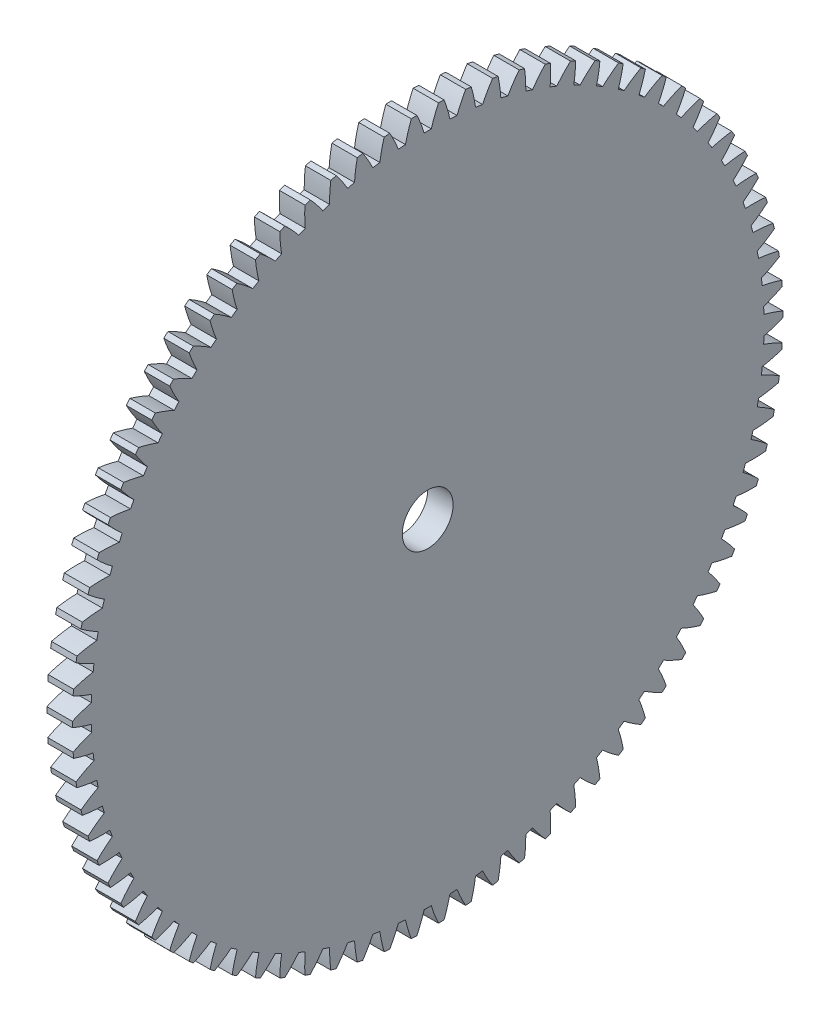
SolidWorks part; units mm, degrees
ref_plane "Plane1" through (0, 0, 0) normal (0, 0, 1) x (1, 0, 0)
ref_plane "Plane2" through (0, 0, 0) normal (0, 1, 0) x (1, 0, 0)
ref_plane "Plane3" through (0, 0, 0) normal (1, 0, 0) x (0, 0, -1)
sketch "HoldingSke" plane through (0, 0, 0) normal (0, 1, 0) x (1, 0, 0)
  line L0 (0, 0) -> (0.1392, -0.9903)
  line L1 (-15, 0) -> (100, 0) construction
  line L2 (0, 0) -> (-2.1039, 2.3779)
  line L3 (0, 0) -> (-11.863, 4.5341)
  line L4 (0, 0) -> (1.2019, 8.552)
  line L5 (0, 0) -> (-46.8476, -17.4728)
  line L6 (0, 0) -> (-2.4869, -1.6779)
  line L7 (-2.1039, 2.3779) -> (8.6586, 51.2059)
  line L8 (-76.2, 54.61) -> (-75.2, 54.61)
  line L9 (-71.009, 38.7566) -> (-53.1078, 45.2721)
  line L10 (-76.2, 71.12) -> (104.1128, 71.12)
  line L11 (0, 0) -> (-3, 0)
  line L12 (-76.2, 101.6) -> (-76.162, 101.6)
  line L13 (24.9733, 27.94) -> (52.9518, 28.4284)
  line L14 (24.9733, 27.94) -> (24.9743, 27.94)
  line L15 (24.9733, 27.94) -> (100.4006, 29.5858)
  line L16 (-63.627, -1) -> (-12.827, -1)
  circle A0 centre (0, 0) radius 3
  circle A1 centre (0, 0) radius 37.5
  circle A2 centre (0, 0) radius 37.5
  circle A3 centre (0, 0) radius 3
  dimension "MHD" = 75
  dimension "Hub_dia" = 75
  dimension "Bore" = 6
  dimension "MBD" = 6
  dimension "Num_teeth" = 82
  dimension "Pitch" = 1
  dimension "Overall_len" = 50
  dimension "Show_teeth" = 82
  dimension "Thickness" = 3
  dimension "OAL" = 50.0001
  dimension "T_dim" = 1
  dimension "Ap" = 20
  dimension "H" = 19.05
  dimension "Pitch_radius" = 180.3128
  dimension "Width" = 3
  dimension "Backlash" = 0.038
  dimension "Addendum_fac" = 1
  dimension "Dedendum_fac" = 1.25
  dimension "Clearance_fac" = 0.25
  dimension "Dedendum_add" = 0.001
  dimension "Module" = 1
sketch "BasProSke" plane through (0, 0, 0) normal (0, 1, 0) x (1, 0, 0)
  line L0 (-10, 0) -> (60, 0) construction
  line L1 (0, 0) -> (0, 42)
  line L2 (0, 0) -> (3, 0)
  line L3 (3, 0) -> (3, 42)
  line L4 (3, 42) -> (0, 42)
  dimension "Thickness" = 3
  dimension "Diameter" = 84
revolve "Base-Revolve" add sketch "BasProSke" angle 360 about L0
sketch "TooCutSke" plane through (0, 0, 0) normal (1, 0, 0) x (0, 0, -1)
  line L1 (0, 0) -> (0, 107) construction
  line L2 (0, 0) -> (-0.8518, 40.9911) construction
  line L3 (0, 0) -> (-3.1403, 81.9272) construction
  line L4 (-0.8518, 40.9911) -> (-1.5702, 40.9636) construction
  arc A0 (0.4198, 39.7468) -> (-0.4198, 39.7468) centre (0, 0) ccw
  arc A1 (1.2904, 42.0056) -> (-1.2904, 42.0056) centre (0, 0) ccw
  circle A2 centre (0, 0) radius 41 construction
  circle A3 centre (0, 0) radius 38.5274 construction
  arc A4 (-0.4198, 39.7468) -> (-1.2904, 42.0056) centre (-16.1163, 34.9947) ccw
  arc A5 (1.2904, 42.0056) -> (0.4198, 39.7468) centre (16.1163, 34.9947) ccw
  dimension "Root_dia" = 79.498
  dimension "Overcut_dia" = 84.0508
  dimension "Pitch_dia" = 82
  dimension "Base_dia" = 77.0548
  dimension "Flank_rad" = 16.4
  dimension "Half_ang" = 2.195
  dimension "Half_CT" = 0.7189
extrude "ToothCut" cut sketch "TooCutSke" along normal through all
fillet "Breaks" [suppressed] radius 0.02 tangent propagation no
fillet "RootFillets" [suppressed] radius 0.251
pattern_circular "TeethCuts" count 82 over 360 about axis through (-10, 0, 0) along (1, 0, 0) of "ToothCut", "RootFillets", "Breaks"
sketch "HubNeaOneSke" plane through (0, 0, 0) normal (-1, 0, 0) x (0, 0, 1)
  circle A0 centre (0, 0) radius 37.5
  dimension "Diameter" = 75
extrude "HubNearOne" [suppressed] add sketch "HubNeaOneSke" along normal blind 47.0001
sketch "HubNeaBotSke" plane through (0, 0, 0) normal (-1, 0, 0) x (0, 0, 1)
  circle A0 centre (0, 0) radius 37.5
  dimension "Diameter" = 75
extrude "HubNearBoth" [suppressed] add sketch "HubNeaBotSke" along normal blind 23.5
ref_plane "FarPln" through (3, 0, 0) normal (1, 0, 0) x (0, 0, -1)
sketch "HubFarSke" plane through (3, 0, 0) normal (1, 0, 0) x (0, 0, -1)
  circle A0 centre (0, 0) radius 37.5
  dimension "Diameter" = 75
extrude "HubFar" [suppressed] add sketch "HubFarSke" along normal blind 23.5
sketch "BorSke" plane through (0, 0, 0) normal (1, 0, 0) x (0, 0, -1)
  circle A0 centre (0, 0) radius 3
  dimension "Diameter" = 6
extrude "Bore" cut sketch "BorSke" along normal mid plane 100.0001
sketch "KeySke" plane through (0, 0, 0) normal (1, 0, 0) x (0, 0, -1)
  line L0 (-1, 0) -> (-1, 4)
  line L1 (-1, 4) -> (1, 4)
  line L2 (1, 4) -> (1, 0)
  line L3 (0, 0) -> (0, 34) construction
  line L4 (-1, 0) -> (1, 0)
  dimension "Offset" = 4
  dimension "Width" = 2
extrude "Keyway" [suppressed] cut sketch "KeySke" along normal mid plane 100.0001
pattern_circular "Keyway2" [suppressed] count 2 every 90 about axis through (-10, 0, 0) along (1, 0, 0) reverse direction yes
sketch "Sketch1" plane through (3, 0, 0) normal (1, 0, 0) x (0, 0, -1)
  circle A0 centre (0, 0) radius 3 construction
  circle A1 centre (0, 0) radius 3
extrude "Boss-Extrude1" add sketch "Sketch1" against normal up to surface (3 mm away) up to face at (0, 0, -3)
sketch "Sketch2" plane through (3, 0, 0) normal (1, 0, 0) x (0, 0, -1)
  line L0 (-1.8, 2.0125) -> (-1.8, -2.0125)
  line L1 (1.8, 2.0125) -> (1.8, -2.0125)
  line L2 (-1.8, 0) -> (1.8, 0) construction
  circle A0 centre (0, 0) radius 2.7
  point P9 (0, 0)
  dimension "D1" = 5.4
  dimension "D2" = 3.6
extrude "Cut-Extrude1" cut sketch "Sketch2" against normal up to surface (3 mm away) contours L0 L2 L1 A0 | L2 L0 A0 L1 region at (3, 1.25, 0) region at (3, -1.25, 0) up to face at (0, 0, 0)
sketch "Sketch3" plane through (3, 0, 0) normal (1, 0, 0) x (0, 0, -1)
  circle A0 centre (0, 0) radius 3
  dimension "D1" = 6
extrude "Cut-Extrude2" cut sketch "Sketch3" against normal up to surface (3 mm away) up to face at (0, 0, 0)
equation "' \"Module@HoldingSke\" = 6.35"
equation "' \"Num_teeth@HoldingSke\" = 12"
equation "' \"Ap@HoldingSke\" =  20"
equation "' \"Ap@HoldingSke\" = 20"
equation "' \"Width@HoldingSke\" = 0.5 * 25.4"
equation "' \"Hub_dia@HoldingSke\"= 1 * 25.4"
equation "' \"Hub_dia@HoldingSke\" = 1 * 25.4"
equation "' \"Overall_len@HoldingSke\" = 1.0 * 25.4"
equation "' \"Bore@HoldingSke\" = 0.75 * 25.4"
equation "' \"T_dim@HoldingSke\" = 0.1 * 25.4"
equation "' \"Width@KeySke\" = 0.25 * 25.4"
equation "' \"Show_teeth@HoldingSke\" = 13"
equation "' \"Backlash@HoldingSke\" = 0.009 * 25.4"
equation "' \"Addendum_fac@HoldingSke\" = 1.0"
equation "' \"Dedendum_fac@HoldingSke\" = 1.25"
equation "' \"Dedendum_add@HoldingSke\" = 0.00005 * 25.4"
equation "' \"Clearance_fac@HoldingSke\" = 0.25"
equation "\"Pitch@HoldingSke\" = 1 / \"Module@HoldingSke\""
equation "\"Overcut_dia@TooCutSke\" = (\"Num_teeth@HoldingSke\" + 2 * \"Addendum_fac@HoldingSke\") / \"Pitch@HoldingSke\" + 0.002 * 25.4"
equation "\"Pitch_dia@TooCutSke\" = \"Num_teeth@HoldingSke\" / \"Pitch@HoldingSke\""
equation "\"Base_dia@TooCutSke\" = \"Num_teeth@HoldingSke\" / \"Pitch@HoldingSke\" * cos((\"Ap@HoldingSke\"  * 3.14159265 / 180))"
equation "\"Root_dia@TooCutSke\" = (\"Num_teeth@HoldingSke\" + 2) / \"Pitch@HoldingSke\" - 2 * (\"Addendum_fac@HoldingSke\" + \"Dedendum_fac@HoldingSke\") / \"Pitch@HoldingSke\" - \"Dedendum_add@HoldingSke\" * 2"
equation "\"Half_ang@TooCutSke\" = 180 / \"Num_teeth@HoldingSke\""
equation "\"Half_CT@TooCutSke\" = \"Num_teeth@HoldingSke\" / \"Pitch@HoldingSke\" * sin((3.14159265 / 2 / \"Num_teeth@HoldingSke\")) / 2 - 7 * \"Backlash@HoldingSke\" / 4"
equation "\"Flank_rad@TooCutSke\" = \"Num_teeth@HoldingSke\" / \"Pitch@HoldingSke\" / 5"
equation "\"Radius@RootFillets\" = \"Clearance_fac@HoldingSke\" / \"Pitch@HoldingSke\" + \"Dedendum_add@HoldingSke\""
equation "\"Break_rad@Breaks\" = 0.02 / \"Pitch@HoldingSke\""
equation "\"Thickness@HoldingSke\" = \"Width@HoldingSke\""
equation "\"OAL@HoldingSke\" = \"Thickness@HoldingSke\""
equation "\"MHD@HoldingSke\" = (\"Num_teeth@HoldingSke\" + 2) / \"Pitch@HoldingSke\" - 2 * (\"Addendum_fac@HoldingSke\" + \"Dedendum_fac@HoldingSke\")  / \"Pitch@HoldingSke\" - \"Dedendum_add@HoldingSke\" * 2"
equation "\"MBD@HoldingSke\" = (\"Num_teeth@HoldingSke\" + 2) / \"Pitch@HoldingSke\" - 2 * (\"Addendum_fac@HoldingSke\" + \"Dedendum_fac@HoldingSke\")  / \"Pitch@HoldingSke\" - \"Dedendum_add@HoldingSke\" * 2 - 0.002 * 25.4"
equation "\"MHD@HoldingSke\" = ((sgn( \"MHD@HoldingSke\" - \"Hub_dia@HoldingSke\" )-1)*( \"MHD@HoldingSke\" - \"Hub_dia@HoldingSke\" ))/-2+ \"Hub_dia@HoldingSke\""
equation "\"MBD@HoldingSke\" = ((sgn( \"MBD@HoldingSke\" - \"Bore@HoldingSke\" )-1)*( \"MBD@HoldingSke\" - \"Bore@HoldingSke\" ))/-2+ \"Bore@HoldingSke\""
equation "\"OAL@HoldingSke\" = ((sgn( \"OAL@HoldingSke\" - \"Overall_len@HoldingSke\" )+1)*( \"OAL@HoldingSke\" - \"Overall_len@HoldingSke\" ))/2 + \"Overall_len@HoldingSke\" + 0.000002 * 25.4"
equation "\"Num_teeth@TeethCuts\" = int( \"Show_teeth@HoldingSke\" ) + 1"
equation "\"Num_teeth@TeethCuts\" = ((sgn( \"Num_teeth@TeethCuts\" - \"Num_teeth@HoldingSke\" )-1)*( \"Num_teeth@TeethCuts\" - \"Num_teeth@HoldingSke\" ))/-2+ \"Num_teeth@HoldingSke\""
equation "\"Num_teeth@TeethCuts\" = ((sgn( \"Num_teeth@TeethCuts\" - 2.0)+1)*( \"Num_teeth@TeethCuts\" - 2.0))/2 +2.0"
equation "\"Angle@TeethCuts\" = 360.0 / \"Num_teeth@HoldingSke\""
equation "\"Diameter@BasProSke\" = (\"Num_teeth@HoldingSke\" + 2 * \"Addendum_fac@HoldingSke\") / \"Pitch@HoldingSke\""
equation "\"Thickness@BasProSke\"  = \"Thickness@HoldingSke\""
equation "' \"Fillet_rad@BasProSke\" =  \"Thickness@HoldingSke\" * 0.05"
equation "' \"Fillet_rad@BasProSke\" = \"Thickness@HoldingSke\" * 0.05"
equation "\"MHD@HoldingSke\" = ((sgn( \"MHD@HoldingSke\" - \"Root_dia@TooCutSke\" )-1)*( \"MHD@HoldingSke\" - \"Root_dia@TooCutSke\" ))/-2+ \"Root_dia@TooCutSke\""
equation "\"Diameter@HubNeaOneSke\" = \"MHD@HoldingSke\""
equation "\"Length@HubNearOne\" = \"OAL@HoldingSke\" - \"Thickness@BasProSke\""
equation "\"Diameter@HubNeaBotSke\" = \"MHD@HoldingSke\""
equation "\"Length@HubNearBoth\" = ( \"OAL@HoldingSke\" - \"Thickness@BasProSke\" ) / 2.0"
equation "\"Thickness@FarPln\" = \"Thickness@BasProSke\""
equation "\"Diameter@HubFarSke\" = \"MHD@HoldingSke\""
equation "\"Length@HubFar\" = ( \"OAL@HoldingSke\" - \"Thickness@BasProSke\" ) / 2.0"
equation "\"Diameter@BorSke\" = \"MBD@HoldingSke\""
equation "\"D1@Bore\" = \"OAL@HoldingSke\" * 2.0"
equation "\"D1@Keyway\" = \"OAL@HoldingSke\" * 2.0"
equation "\"Offset@KeySke\" = \"T_dim@HoldingSke\" + \"MBD@HoldingSke\" / 2.0"
